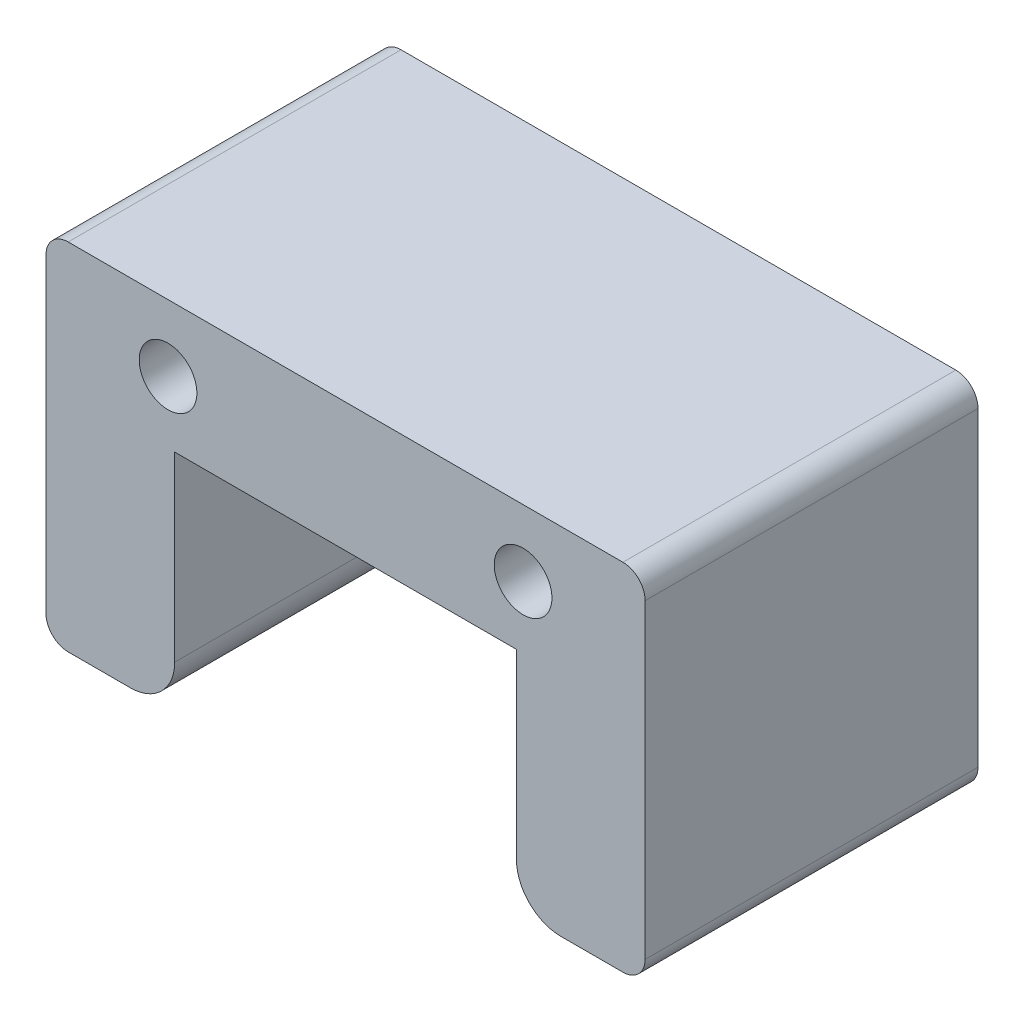
SolidWorks part; units mm, degrees
ref_plane "正面" through (0, 0, 0) normal (0, 0, 1) x (1, 0, 0)
ref_plane "平面" through (0, 0, 0) normal (0, 1, 0) x (1, 0, 0)
ref_plane "右側面" through (0, 0, 0) normal (1, 0, 0) x (0, 0, -1)
sketch "ｽｹｯﾁ1" plane through (0, 0, 0) normal (0, 0, 1) x (1, 0, 0)
  line L0 (0, 5) -> (0, -5) construction
  line L1 (-7.5, 5) -> (7.5, 5)
  line L2 (-7.5, 5) -> (-7.5, -5)
  line L3 (-7.5, -5) -> (7.5, -5)
  line L4 (7.5, 5) -> (7.5, -5)
  line L5 (-7.5, 5) -> (7.5, -5) construction
  line L6 (-7.5, -5) -> (7.5, 5) construction
  line L7 (0, 11) -> (0, 5) construction
  line L8 (-13.5, -5) -> (13.5, -5)
  line L9 (-13.5, -5) -> (-13.5, 11)
  line L10 (-13.5, 11) -> (13.5, 11)
  line L11 (13.5, -5) -> (13.5, 11)
  line L12 (-13.5, -5) -> (13.5, 11) construction
  line L13 (-13.5, 11) -> (13.5, -5) construction
  line L14 (0, 8) -> (8, 8) construction
  circle A0 centre (8, 8) radius 1.3
  circle A1 centre (-8, 8) radius 1.3
  point P0 (0, 0)
  point P8 (0, 3)
  dimension "D5" = 2.6
  dimension "D1" = 15
  dimension "D2" = 10
  dimension "D3" = 6
  dimension "D4" = 6
  dimension "D6" = 16
extrude "ﾎﾞｽ - 押し出し1" add sketch "ｽｹｯﾁ1" along normal blind 15 contours L8 L11 L10 L9 L2 L1 L4 A0 A1 region at (-7.8138, 0, 0)
ref_plane "平面1" through (0, 6, 0) normal (0, -1, 0) x (-1, 0, 0)
sketch "ｽｹｯﾁ2" plane through (0, 6, 0) normal (0, -1, 0) x (-1, 0, 0)
  line L0 (0, 0) -> (0, -15) construction
  line L1 (7.5, -15) -> (-7.5, -15) construction
  line L2 (-4.15, -3.35) -> (-4.15, -4.35) construction
  line L3 (-3.15, -3.35) -> (3.15, -3.35)
  line L4 (-4.15, -4.35) -> (-4.15, -10.65)
  line L5 (-3.15, -11.65) -> (3.15, -11.65)
  line L6 (4.15, -4.35) -> (4.15, -10.65)
  line L7 (-4.15, -3.35) -> (4.15, -11.65) construction
  line L8 (-4.15, -11.65) -> (4.15, -3.35) construction
  line L9 (-4.15, -3.35) -> (-3.15, -3.35) construction
  line L10 (4.15, -3.35) -> (4.15, -4.35) construction
  line L11 (3.15, -3.35) -> (4.15, -3.35) construction
  line L12 (-4.15, -10.65) -> (-4.15, -11.65) construction
  line L13 (-4.15, -11.65) -> (-3.15, -11.65) construction
  line L14 (3.15, -11.65) -> (4.15, -11.65) construction
  line L15 (4.15, -10.65) -> (4.15, -11.65) construction
  arc A1 (4.15, -4.35) -> (3.15, -3.35) centre (4.15, -3.35) ccw
  arc A2 (3.15, -11.65) -> (4.15, -10.65) centre (4.15, -11.65) ccw
  arc A3 (-4.15, -10.65) -> (-3.15, -11.65) centre (-4.15, -11.65) ccw
  arc A4 (-3.15, -3.35) -> (-4.15, -4.35) centre (-4.15, -3.35) ccw
  arc A5 (-4.15, -4.35) -> (-3.4429, -4.0571) centre (-4.15, -3.35) ccw construction
  arc A6 (-3.4429, -4.0571) -> (-3.15, -3.35) centre (-4.15, -3.35) ccw construction
  arc A7 (3.4429, -4.0571) -> (4.15, -4.35) centre (4.15, -3.35) ccw construction
  arc A8 (3.15, -3.35) -> (3.4429, -4.0571) centre (4.15, -3.35) ccw construction
  arc A9 (-3.4429, -10.9429) -> (-4.15, -10.65) centre (-4.15, -11.65) ccw construction
  arc A10 (-3.15, -11.65) -> (-3.4429, -10.9429) centre (-4.15, -11.65) ccw construction
  arc A11 (3.4429, -10.9429) -> (3.15, -11.65) centre (4.15, -11.65) ccw construction
  arc A12 (4.15, -10.65) -> (3.4429, -10.9429) centre (4.15, -11.65) ccw construction
  point P5 (0, -7.5)
  point P19 (0, -7.5)
  dimension "D1" = 8.3
  dimension "D4" = 2
  dimension "D2" = 8.3
  dimension "D3" = 4
extrude "ｶｯﾄ - 押し出し1" [suppressed] cut sketch "ｽｹｯﾁ2" against normal blind 3.1
fillet "ﾌｨﾚｯﾄ1" radius 1 4 edges at (13.5, 11, 7.5) (-13.5, 11, 7.5) (13.5, -5, 7.5) (-13.5, -5, 7.5)
sketch "ｽｹｯﾁ3" plane through (0, 0, 15) normal (0, 0, 1) x (1, 0, 0)
  line L9 (7.7, -5) -> (7.7, 5.2)
  line L10 (-7.7, 5.2) -> (-7.7, -5)
  line L11 (7.7, 5.2) -> (-7.7, 5.2)
  line L12 (7.7, -5) -> (7.7, 5.2)
  line L13 (-7.7, 5.2) -> (-7.7, -5)
  line L14 (7.7, 5.2) -> (-7.7, 5.2)
  dimension "D1" = 0.2
extrude "ｶｯﾄ - 押し出し2" cut sketch "ｽｹｯﾁ3" against normal through all and the other way through all
fillet "ﾌｨﾚｯﾄ2" radius 2 2 edges at (7.7, -5, 7.5) (-7.7, -5, 7.5)
sketch "ｽｹｯﾁ5" plane through (0, 6, 0) normal (0, -1, 0) x (-1, 0, 0)
  line L0 (0, 0) -> (0, -15) construction
  line L1 (7.7, -15) -> (-7.7, -15) construction
  circle A0 centre (0, -7.5) radius 3.15
  dimension "D1" = 6.3
extrude "ｶｯﾄ - 押し出し3" cut sketch "ｽｹｯﾁ5" against normal blind 2.8
